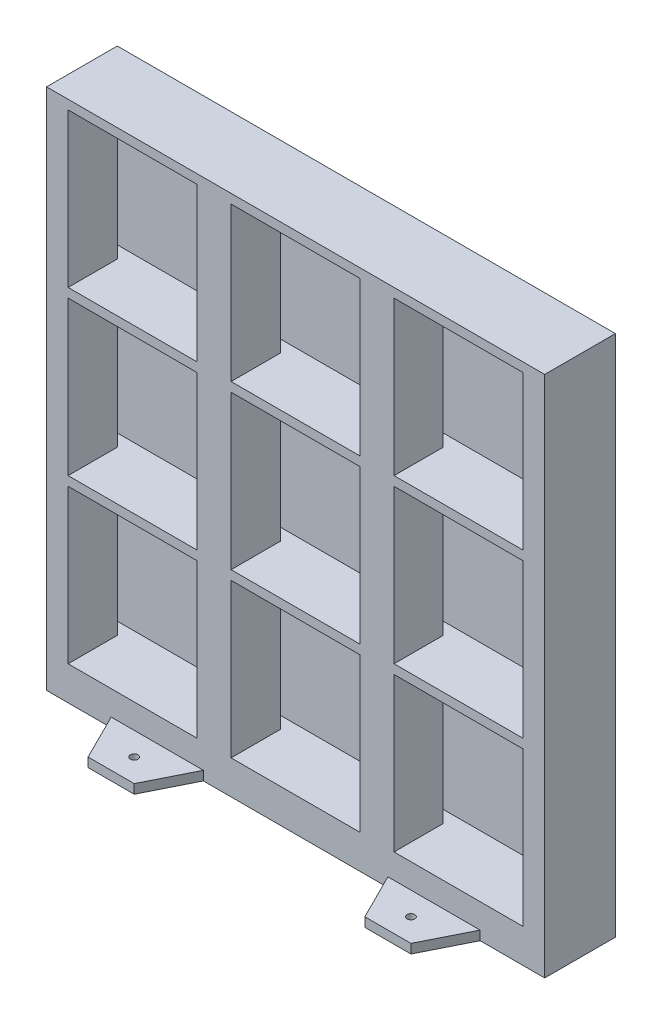
SolidWorks part; units mm, degrees
ref_plane "Front Plane" through (0, 0, 0) normal (0, 0, 1) x (1, 0, 0)
ref_plane "Top Plane" through (0, 0, 0) normal (0, 1, 0) x (1, 0, 0)
ref_plane "Right Plane" through (0, 0, 0) normal (1, 0, 0) x (0, 0, -1)
sketch "Sketch1" plane through (0, 0, 0) normal (0, 0, 1) x (1, 0, 0)
  line L1 (83.2209, 52.407) -> (-78.7791, 52.407)
  line L2 (83.2209, 52.407) -> (83.2209, -109.593)
  line L3 (83.2209, -109.593) -> (-78.7791, -109.593)
  line L4 (-78.7791, 52.407) -> (-78.7791, -109.593)
  line L5 (-75.7791, 49.407) -> (-25.7791, 49.407)
  line L6 (-75.7791, 49.407) -> (-75.7791, -0.593)
  line L7 (-75.7791, -0.593) -> (-25.7791, -0.593)
  line L8 (-25.7791, 49.407) -> (-25.7791, -0.593)
  line L9 (-22.7791, 49.407) -> (27.2209, 49.407)
  line L10 (-22.7791, 49.407) -> (-22.7791, -0.593)
  line L11 (-22.7791, -0.593) -> (27.2209, -0.593)
  line L12 (27.2209, 49.407) -> (27.2209, -0.593)
  line L13 (30.2209, 49.407) -> (80.2209, 49.407)
  line L14 (30.2209, 49.407) -> (30.2209, -0.593)
  line L15 (30.2209, -0.593) -> (80.2209, -0.593)
  line L16 (80.2209, 49.407) -> (80.2209, -0.593)
  line L17 (-75.7791, -3.593) -> (-25.7791, -3.593)
  line L18 (-75.7791, -3.593) -> (-75.7791, -53.593)
  line L19 (-75.7791, -53.593) -> (-25.7791, -53.593)
  line L20 (-25.7791, -3.593) -> (-25.7791, -53.593)
  line L21 (-22.7791, -3.593) -> (27.2209, -3.593)
  line L22 (-22.7791, -3.593) -> (-22.7791, -53.593)
  line L23 (-22.7791, -53.593) -> (27.2209, -53.593)
  line L24 (27.2209, -3.593) -> (27.2209, -53.593)
  line L25 (30.2209, -3.593) -> (80.2209, -3.593)
  line L26 (30.2209, -3.593) -> (30.2209, -53.593)
  line L27 (30.2209, -53.593) -> (80.2209, -53.593)
  line L28 (80.2209, -3.593) -> (80.2209, -53.593)
  line L29 (-75.7791, -56.593) -> (-25.7791, -56.593)
  line L30 (-75.7791, -56.593) -> (-75.7791, -106.593)
  line L31 (-75.7791, -106.593) -> (-25.7791, -106.593)
  line L32 (-25.7791, -56.593) -> (-25.7791, -106.593)
  line L33 (-22.7791, -56.593) -> (27.2209, -56.593)
  line L34 (-22.7791, -56.593) -> (-22.7791, -106.593)
  line L35 (-22.7791, -106.593) -> (27.2209, -106.593)
  line L36 (27.2209, -56.593) -> (27.2209, -106.593)
  line L37 (30.2209, -56.593) -> (80.2209, -56.593)
  line L38 (30.2209, -56.593) -> (30.2209, -106.593)
  line L39 (30.2209, -106.593) -> (80.2209, -106.593)
  line L40 (80.2209, -56.593) -> (80.2209, -106.593)
  point P41 (0, 0)
  dimension "D1" = 162
  dimension "D2" = 162
  dimension "D3" = 3
  dimension "D4" = 3
  dimension "D5" = 3
  dimension "D6" = 3
  dimension "D7" = 50
  dimension "D8" = 3
  dimension "D9" = 3
extrude "Boss-Extrude1" add sketch "Sketch1" along normal blind 23
extrude "Boss-Extrude2" add sketch "Sketch1<2>" along normal blind 3 contours L8 L5 L6 L7 | L12 L9 L10 L11 | L16 L13 L14 L15 | L28 L25 L26 L27 | L24 L21 L22 L23 | L20 L17 L18 L19 | L32 L29 L30 L31 | L36 L33 L34 L35 | L40 L37 L38 L39 | L1 L4 L3 L2 L5 L8 L7 L6 L9 L12 L11 L10 L13 L16 L15 L14 L17 L20 L19 L18 L21 L24 L23 L22 L25 L28 L27 L26 L29 L32 L31 L30 L33 L36 L35 L34 L37 L40 L39 L38 region at (80.9299, -28.593, 0) region at (-50.7791, 24.407, 0) region at (2.2209, 24.407, 0) region at (55.2209, 24.407, 0) region at (-50.7791, -28.593, 0) region at (2.2209, -28.593, 0) region at (55.2209, -28.593, 0) region at (-50.7791, -81.593, 0) region at (2.2209, -81.593, 0) region at (55.2209, -81.593, 0)
sketch "Sketch1<2>" plane through (0, 0, 0) normal (0, 0, 1) x (1, 0, 0) same geometry as "Sketch1"
sketch "Sketch2" plane through (0, 0, 23) normal (0, 0, 1) x (1, 0, 0)
  line L0 (-75.7791, -0.593) -> (-25.7791, -0.593) construction
  line L1 (-25.7791, 49.407) -> (-29.7791, 49.407)
  line L2 (-25.7791, 49.407) -> (-25.7791, -0.593)
  line L3 (-25.7791, -0.593) -> (-29.7791, -0.593)
  line L4 (-29.7791, 49.407) -> (-29.7791, -0.593)
  line L5 (-75.7791, -0.593) -> (-25.7791, -0.593) construction
  line L6 (-75.7791, 49.407) -> (-71.7791, 49.407)
  line L7 (-75.7791, 49.407) -> (-75.7791, -0.593)
  line L8 (-75.7791, -0.593) -> (-71.7791, -0.593)
  line L9 (-71.7791, 49.407) -> (-71.7791, -0.593)
  dimension "D1" = 4
  dimension "D2" = 4
extrude "Boss-Extrude3" add sketch "Sketch2" against normal blind 16
pattern_linear "LPattern1" count 3 spacing 53 along (1, 0, 0) of "Boss-Extrude3"
pattern_linear "LPattern2" count 3 spacing 53 along (0, -1, 0) of "LPattern1"
sketch "Sketch5" plane through (0, -109.593, 0) normal (0, -1, 0) x (1, 0, 0)
  line L1 (-78.7791, 23) -> (83.2209, 23)
  line L2 (-78.7791, 23) -> (-78.7791, 0)
  line L3 (-78.7791, 0) -> (83.2209, 0)
  line L4 (83.2209, 23) -> (83.2209, 0)
extrude "Boss-Extrude5" add sketch "Sketch5" along normal blind 8
sketch "Sketch3" plane through (0, -109.593, 0) normal (0, -1, 0) x (1, 0, 0)
  line L0 (-78.7791, 23) -> (-78.7791, 0) construction
  line L5 (83.2209, 0) -> (83.2209, 23) construction
  line L19 (-78.7791, 23) -> (83.2209, 23) construction
  line L20 (-50.2791, 23) -> (-35.2791, 23)
  line L21 (-50.2791, 23) -> (-50.2791, 38)
  line L22 (-50.2791, 38) -> (-35.2791, 38)
  line L23 (-35.2791, 23) -> (-35.2791, 38)
  line L24 (-50.2791, 38) -> (-57.7791, 23)
  line L25 (54.7209, 23) -> (39.7209, 23)
  line L26 (54.7209, 23) -> (54.7209, 38)
  line L27 (54.7209, 38) -> (39.7209, 38)
  line L28 (39.7209, 23) -> (39.7209, 38)
  line L29 (-57.7791, 23) -> (-50.2791, 23)
  line L30 (-35.2791, 23) -> (-27.7791, 23)
  line L31 (-27.7791, 23) -> (-35.2791, 38)
  line L32 (39.7209, 38) -> (32.2209, 23)
  line L33 (32.2209, 23) -> (39.7209, 23)
  line L34 (54.7209, 23) -> (62.2209, 23)
  line L35 (62.2209, 23) -> (54.7209, 38)
  circle A0 centre (-42.7791, 30.5) radius 1.25
  circle A1 centre (47.2209, 30.5) radius 1.25
  point P10 (0, 0)
  point P11 (0, 0)
  dimension "D4" = 2.5
  dimension "D8" = 7.5
  dimension "D9" = 7.5
  dimension "D1" = 7.5
  dimension "D2" = 28.5
  dimension "D3" = 28.5
  dimension "D5" = 7.5
  dimension "D6" = 15
  dimension "D7" = 15
extrude "Boss-Extrude4" add sketch "Sketch3" against normal blind 3 from offset 8 contours L21 L24 | L23 L22 L21 A0 | L31 L23 | L28 L32 | L28 L26 L27 A1 | L35 L26 region at (-50.0669, -109.593, 30.5) region at (-52.7791, -109.593, 28) region at (-32.7791, -109.593, 28) region at (47.2209, -109.593, 23.2121) region at (57.2209, -109.593, 28) region at (37.2209, -109.593, 28)
